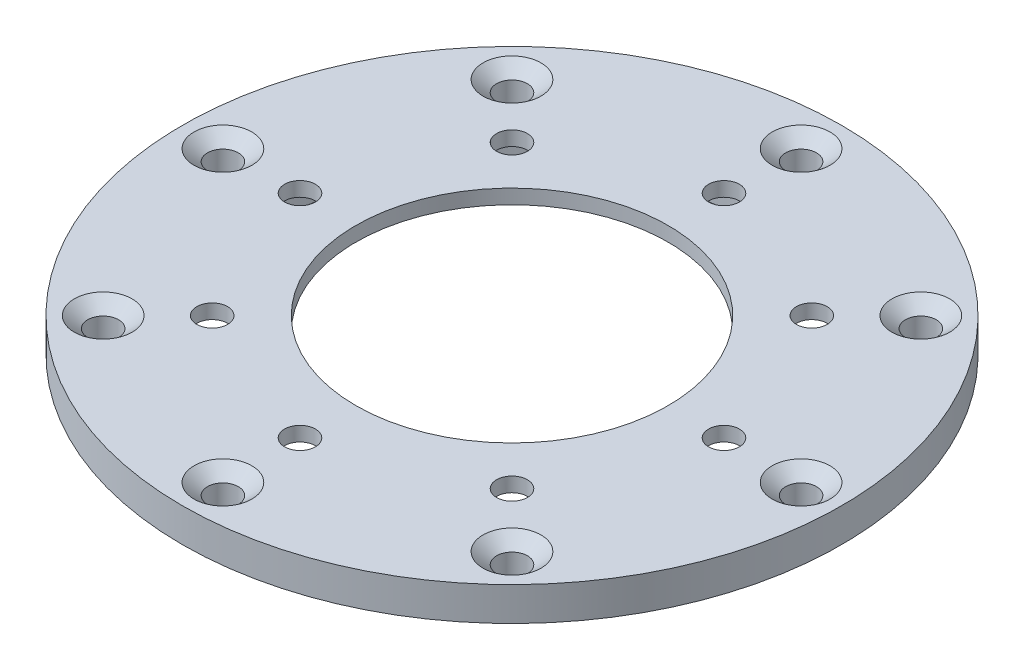
SolidWorks part; units mm, degrees
ref_plane "Front Plane" through (0, 0, 0) normal (0, 0, 1) x (1, 0, 0)
ref_plane "Top Plane" through (0, 0, 0) normal (0, 1, 0) x (1, 0, 0)
ref_plane "Right Plane" through (0, 0, 0) normal (1, 0, 0) x (0, 0, -1)
ref_axis "Axe2" through (0, 37.3734, 0) along (0, -1, 0)
sketch "Esquisse2" plane through (0, 0, 0) normal (0, 0, 1) x (1, 0, 0)
  line L0 (34.2, 0) -> (34.2, 3.5)
  line L3 (34.2, 3.5) -> (16.2, 3.5)
  line L4 (16.2, 3.5) -> (16.2, 2)
  line L5 (24.2, 0) -> (34.2, 0)
  line L6 (16.2, 2) -> (24.2, 2)
  line L7 (24.2, 2) -> (24.2, 0)
  point P2 (29.2, 3)
  point P8 (0, 0)
  dimension "D1" = 24.2
  dimension "D2" = 10
  dimension "D3" = 16.2
  dimension "D4" = 2
  dimension "D5" = 1.5
revolve "Révolution1" add sketch "Esquisse2" angle 360 about axis through (0, 37.3734, 0) along (0, -1, 0)
sketch "Esquisse3" plane through (0, 3.5, 0) normal (0, 1, 0) x (1, 0, 0)
  circle A0 centre (22, 0) radius 1.6
  point P2 (0, 0)
  point P6 (0, 0)
  point P7 (0, 0)
  dimension "D1" = 3.2
  dimension "D2" = 22
extrude "Enlèv. mat.-Extru.1" cut sketch "Esquisse3" against normal through all
hole_wizard "Fraisage pour vis à tête fraisée (100) #01" positions "Esquisse4" profile "Esquisse5" countersink size "#0" standard "Ansi Inch" end condition through all
sketch "Esquisse4" plane through (0, 3.5, 0) normal (0, 1, 0) x (1, 0, 0)
  point P0 (30, 0)
  point P4 (0, 0)
  dimension "D1" = 30
sketch "Esquisse5" plane through (30, 3.5, 0) normal (1, 0, 0) x (0, 0, 1)
  line L0 (0, 0) -> (0, 3.5)
  line L1 (0, 3.5) -> (1.6, 3.5)
  line L2 (1.6, 3.5) -> (1.6, 1.1747)
  line L3 (1.6, 1.1747) -> (3, 0)
  line L5 (3, 0) -> (0, 0)
  line L6 (-1.6, 1.1747) -> (-3, 0) construction
  line L11 (0, -6.35) -> (0, 107.95) construction
  dimension "Diamètre du perçage jusqu'au prochain" = 3.2
  dimension "Profondeur du perçage jusqu'au prochain" = 3.5
  dimension "Diamètre du fraisage entrant" = 6
  dimension "Angle du fraisage entrant" = 100
pattern_circular "Répétition circulaire1" count 8 every 45 about axis through (0, 37.3734, 0) along (0, -1, 0) of "Fraisage pour vis à tête fraisée (100) #01", "Enlèv. mat.-Extru.1"
